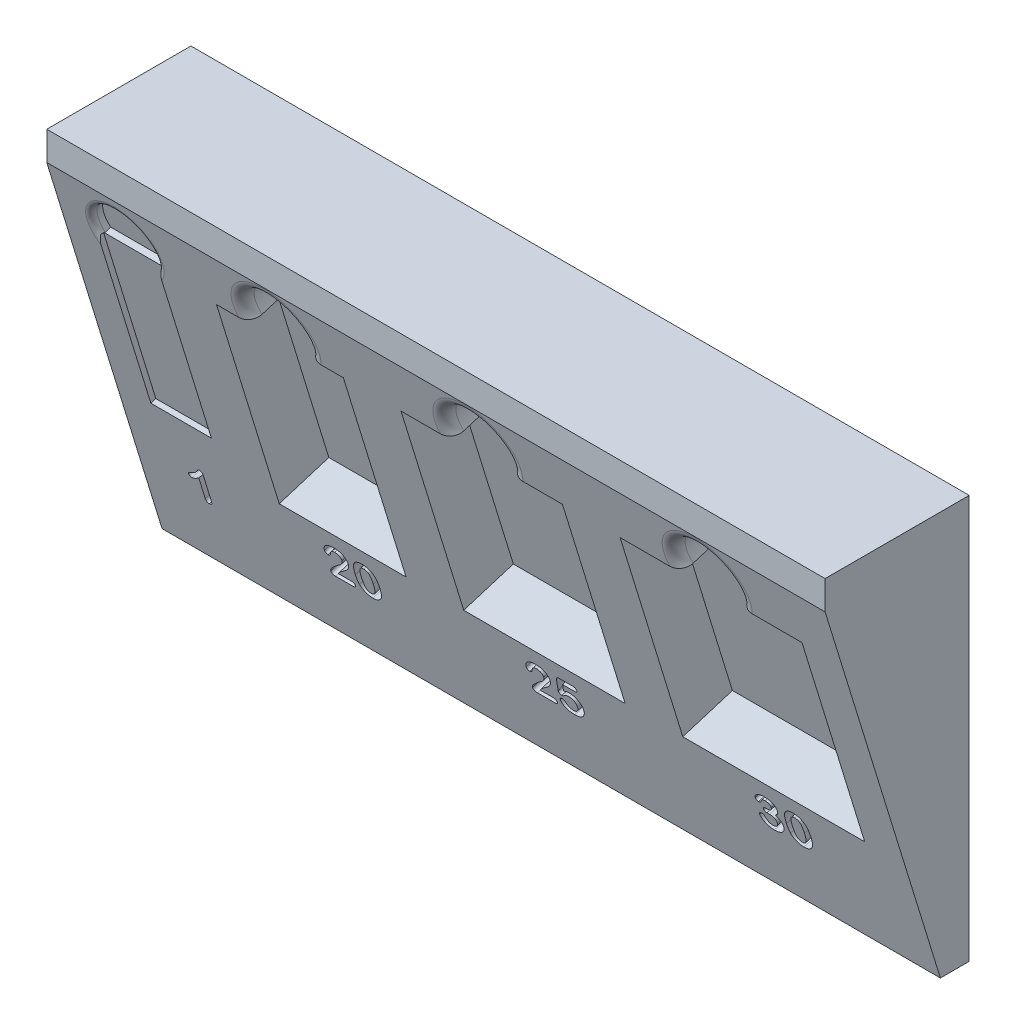
SolidWorks part; units mm, degrees
ref_plane "Top" through (0, 0, 0) normal (0, 0, 1) x (1, 0, 0)
ref_plane "Front" through (0, 0, 0) normal (0, 1, 0) x (1, 0, 0)
ref_plane "Right" through (0, 0, 0) normal (1, 0, 0) x (0, 0, -1)
sketch "Sketch1" plane through (0, 0, 0) normal (0, 0, 1) x (1, 0, 0)
  line L1 (-67.5, -35) -> (67.5, -35)
  line L2 (-67.5, -35) -> (-67.5, 35)
  line L3 (-67.5, 35) -> (67.5, 35)
  line L4 (67.5, -35) -> (67.5, 35)
  line L5 (-67.5, -35) -> (67.5, 35) construction
  line L6 (-67.5, 35) -> (67.5, -35) construction
  point P0 (0, 0)
  dimension "D1" = 70
  dimension "D2" = 135
extrude "Boss-Extrude1" add sketch "Sketch1" along normal blind 25
sketch "Sketch2" plane through (-67.5, 0, 0) normal (-1, 0, 0) x (0, 0, 1)
  line L0 (25, 30) -> (5, -35)
  line L1 (25, 35) -> (25, -35) construction
  line L2 (25, -35) -> (0, -35) construction
  line L3 (25, 35) -> (0, 35) construction
  line L4 (0, 35) -> (0, -35) construction
  line L5 (25, 30) -> (31.5353, -44.5522)
  line L6 (31.5353, -44.5522) -> (5, -35)
  dimension "D1" = 5
  dimension "D2" = 5
extrude "Cut-Extrude1" cut sketch "Sketch2" against normal through all both and the other way through all
sketch "Sketch3" plane through (0, -4.4324, 14.4054) normal (0, -0.2941, 0.9558) x (1, 0, 0)
  line L0 (-67.5, 26.0255) -> (67.5, 26.0255) construction
  line L1 (-67.5, -31.9818) -> (-67.5, 36.0255) construction
  line L2 (67.5, 36.0255) -> (67.5, -31.9818) construction
  line L3 (67.5, 36.0255) -> (-67.5, 36.0255) construction
  line L5 (-61.5, 26.0255) -> (-51, 26.0255)
  line L6 (-61.5, 26.0255) -> (-61.5, -4.9745)
  line L7 (-61.5, -4.9745) -> (-51, -4.9745)
  line L8 (-51, 26.0255) -> (-51, -4.9745)
  line L9 (-41, 26.0255) -> (-19, 26.0255)
  line L10 (-41, 26.0255) -> (-41, -10.9745)
  line L11 (-41, -10.9745) -> (-19, -10.9745)
  line L12 (-19, 26.0255) -> (-19, -10.9745)
  line L13 (-9, 26.0255) -> (19, 26.0255)
  line L14 (-9, 26.0255) -> (-9, -10.9745)
  line L15 (-9, -10.9745) -> (19, -10.9745)
  line L16 (19, 26.0255) -> (19, -10.9745)
  line L17 (29, 26.0255) -> (60.55, 26.0255)
  line L18 (29, 26.0255) -> (29, -10.9745)
  line L19 (29, -10.9745) -> (60.55, -10.9745)
  line L20 (60.55, 26.0255) -> (60.55, -10.9745)
  dimension "D1" = 10
  dimension "D2" = 10.5
  dimension "D3" = 31
  dimension "D4" = 22
  dimension "D5" = 37
  dimension "D6" = 10
  dimension "D7" = 10
  dimension "D8" = 28
  dimension "D9" = 37
  dimension "D10" = 37
  dimension "D11" = 31.55
  dimension "D12" = 10
  dimension "D13" = 6
extrude "Cut-Extrude4" cut sketch "Sketch3" against normal blind 9
sketch "Sketch4" plane through (0, -1.7857, 5.8034) normal (0, -0.2941, 0.9558) x (1, 0, 0)
  line L0 (-51, 26.0255) -> (-61.5, 26.0255) construction
  line L1 (-63.8906, 27.4271) -> (-48.2695, 27.4271)
  line L2 (-63.8906, 27.4271) -> (-63.8906, -7.0957)
  line L3 (-63.8906, -7.0957) -> (-48.2695, -7.0957)
  line L4 (-48.2695, 27.4271) -> (-48.2695, -7.0957)
  line L5 (-51, -4.9745) -> (-51, 26.0255) construction
  line L6 (-61.5, -4.9745) -> (-51, -4.9745) construction
  line L8 (-61.5, 26.0255) -> (-61.5, -4.9745) construction
extrude "Boss-Extrude2" add sketch "Sketch4" along normal blind 8.1
sketch "Sketch5" plane through (0, -4.4324, 14.4054) normal (0, -0.2941, 0.9558) x (1, 0, 0)
  line L0 (-19, 26.0255) -> (-41, 26.0255) construction
  line L1 (-35, 26.0255) -> (-25, 26.0255)
  line L2 (0, 26.0255) -> (10, 26.0255)
  line L3 (39.775, 26.0255) -> (49.775, 26.0255)
  line L5 (-30, -10.9745) -> (-30, 67.6081) construction
  line L6 (-41, -10.9745) -> (-19, -10.9745) construction
  line L7 (5, -10.9745) -> (5, 67.6081) construction
  line L8 (-9, -10.9745) -> (19, -10.9745) construction
  line L9 (44.775, -10.9745) -> (44.775, 67.6081) construction
  line L10 (29, -10.9745) -> (60.55, -10.9745) construction
  arc A0 (-35, 26.0255) -> (-25, 26.0255) centre (-30, 28.3168) cw
  arc A1 (0, 26.0255) -> (10, 26.0255) centre (5, 28.3168) cw
  arc A2 (39.775, 26.0255) -> (49.775, 26.0255) centre (44.775, 28.3168) cw
  point P23 (0, 0)
  point P24 (0, 0)
  dimension "D2" = 5.5
  dimension "D1" = 10
extrude "Cut-Extrude5" cut sketch "Sketch5" against normal blind 10
sketch "Sketch6" plane through (0, -4.4324, 14.4054) normal (0, -0.2941, 0.9558) x (1, 0, 0)
  line L0 (-61.2866, 25.9482) -> (-51.2134, 25.9482)
  line L1 (-56.25, -4.9745) -> (-56.25, 47.5105) construction
  line L2 (-61.5, -4.9745) -> (-51, -4.9745) construction
  arc A0 (-61.2866, 25.9482) -> (-51.2134, 25.9482) centre (-56.25, 28.2395) cw
  point P3 (-56.25, 28.4491)
  point P8 (-56.25, 28.3087)
  point P9 (-56.25, 28.2395)
extrude "Cut-Extrude6" cut sketch "Sketch6" against normal blind 2
sketch "Sketch7" plane through (0, -4.4324, 14.4054) normal (0, -0.2941, 0.9558) x (1, 0, 0)
  line L0 (-56.25, -4.9745) -> (-56.25, 55.1735) construction
  line L1 (-51, -4.9745) -> (-61.5, -4.9745) construction
  line L2 (-30, -10.9745) -> (-30, 55.1735) construction
  line L3 (-41, -10.9745) -> (-19, -10.9745) construction
  line L4 (5, -10.9745) -> (5, 55.1735) construction
  line L5 (-9, -10.9745) -> (19, -10.9745) construction
  line L6 (44.775, -10.9745) -> (44.775, 55.1735) construction
  line L7 (29, -10.9745) -> (60.55, -10.9745) construction
  line L8 (-61.5, -20.0423) -> (-51, -20.0423) construction
  line L9 (-41, -20.0423) -> (-19, -20.0423) construction
  line L10 (-9, -20.0423) -> (19, -20.0423) construction
  line L11 (29, -20.0423) -> (60.55, -20.0423) construction
  line L12 (-61.5, -4.9745) -> (-61.5, 26.0255) construction
  line L13 (-51, -4.9745) -> (-51, 26.0255) construction
  line L14 (-41, 26.0255) -> (-41, -10.9745) construction
  line L15 (-19, -10.9745) -> (-19, 26.0255) construction
  line L16 (-9, 26.0255) -> (-9, -10.9745) construction
  line L17 (19, -10.9745) -> (19, 26.0255) construction
  line L18 (29, 26.0255) -> (29, -10.9745) construction
  line L19 (60.55, -10.9745) -> (60.55, 26.0255) construction
  line L20 (-41, -10.9745) -> (-19, -10.9745) construction
  line L21 (29, -10.9745) -> (60.55, -10.9745) construction
  text T0 "1" font "Arial Rounded MT Bold" height 6.35
  text T1 "20" font "Arial Rounded MT Bold" height 6.35
  text T2 "25" font "Arial Rounded MT Bold" height 6.35
  text T3 "30" font "Arial Rounded MT Bold" height 6.35
  point P26 (0, 0)
extrude "Cut-Extrude7" cut sketch "Sketch7" against normal blind 3
fillet "Fillet1" radius 2 3 edges at (44.775, 27.889, 24.3504) (5, 27.889, 24.3504) (-30, 27.889, 24.3504)
fillet "Fillet2" radius 1 1 edges at (-56.25, 27.8469, 24.3375)
